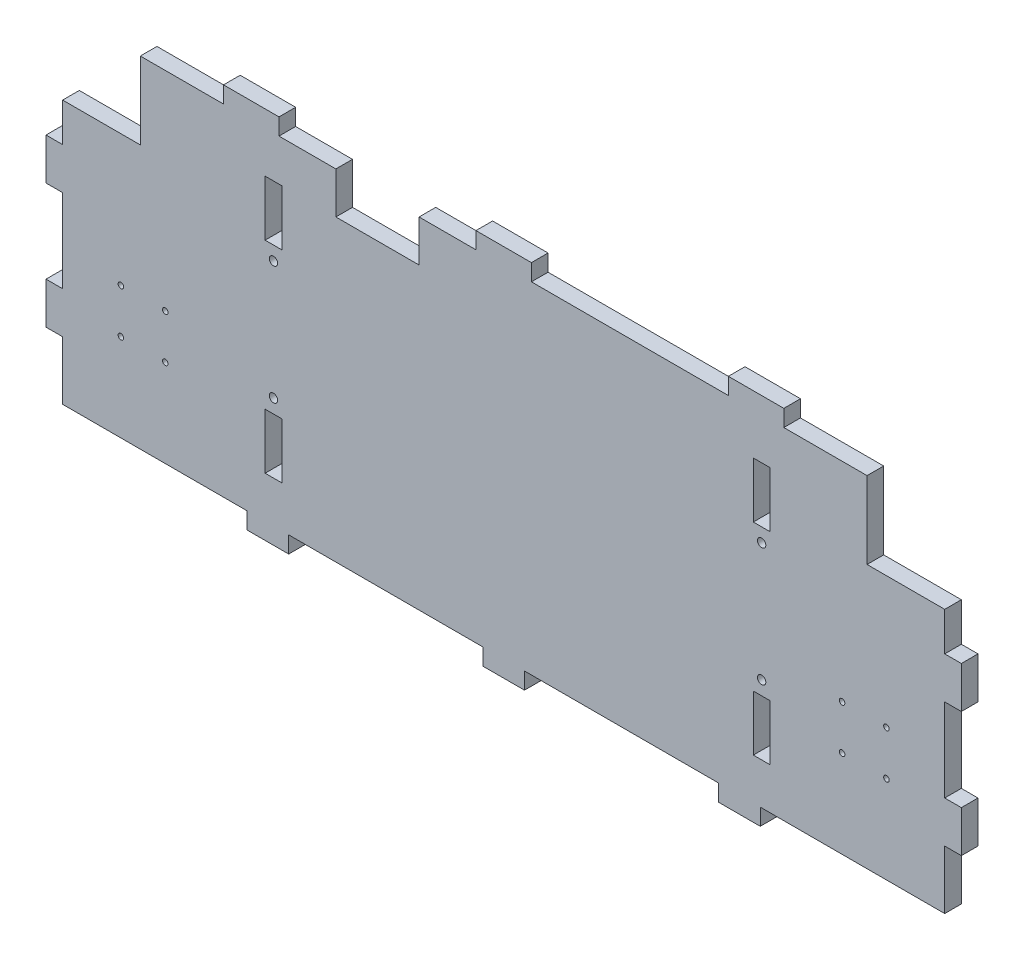
SolidWorks part; units mm, degrees
ref_plane "Plan de face" through (0, 0, 0) normal (0, 0, 1) x (1, 0, 0)
ref_plane "Plan de dessus" through (0, 0, 0) normal (0, 1, 0) x (1, 0, 0)
ref_plane "Plan de droite" through (0, 0, 0) normal (1, 0, 0) x (0, 0, -1)
sketch "Esquisse1" plane through (0, 0, 0) normal (0, 0, 1) x (1, 0, 0)
  line L0 (-159, 35) -> (-131, 35)
  line L1 (0, 102.0551) -> (0, -193.4247) construction
  line L2 (-159, 35) -> (-159, -60)
  line L3 (-159, -60) -> (159, -60)
  line L4 (159, 35) -> (159, -60)
  line L6 (131, 35) -> (131, 62.75)
  line L7 (131, 62.75) -> (-131, 62.75)
  line L8 (-131, 35) -> (-131, 62.75)
  line L9 (159, 35) -> (131, 35)
  line L10 (96, 47.75) -> (90, 47.75)
  line L11 (96, 47.75) -> (96, 27.75)
  line L12 (96, 27.75) -> (90, 27.75)
  line L13 (90, 47.75) -> (90, 27.75)
  line L14 (96, -25.01) -> (90, -25.01)
  line L15 (96, -25.01) -> (96, -45.01)
  line L16 (96, -45.01) -> (90, -45.01)
  line L17 (90, -25.01) -> (90, -45.01)
  line L18 (-80, 47.75) -> (-86, 47.75)
  line L19 (-80, 47.75) -> (-80, 27.75)
  line L20 (-80, 27.75) -> (-86, 27.75)
  line L21 (-86, 47.75) -> (-86, 27.75)
  line L22 (-80, -25.01) -> (-86, -25.01)
  line L23 (-80, -25.01) -> (-80, -45.01)
  line L24 (-80, -45.01) -> (-86, -45.01)
  line L25 (-86, -25.01) -> (-86, -45.01)
  dimension "D1" = 95
  dimension "D2" = 28
  dimension "D3" = 28
  dimension "D4" = 95
  dimension "D6" = 262
  dimension "D7" = 122.75
  dimension "D5" = 159
  dimension "D8" = 318
  dimension "D9" = 6
  dimension "D10" = 20
  dimension "D11" = 20
  dimension "D12" = 6
  dimension "D13" = 6
  dimension "D14" = 20
  dimension "D15" = 6
  dimension "D16" = 20
  dimension "D17" = 52.76
  dimension "D18" = 63
  dimension "D19" = 73
  dimension "D20" = 73
  dimension "D21" = 52.76
  dimension "D22" = 15
  dimension "D23" = 15
  dimension "D24" = 63
extrude "Boss.-Extru.1" add sketch "Esquisse1" along normal blind 6
sketch "Esquisse2" plane through (0, 0, 6) normal (0, 0, 1) x (1, 0, 0)
  line L0 (-159, -60) -> (159, -60) construction
  line L1 (-92.5, -60) -> (-77.5, -60)
  line L2 (-92.5, -60) -> (-92.5, -66)
  line L3 (-92.5, -66) -> (-77.5, -66)
  line L4 (-77.5, -60) -> (-77.5, -66)
  line L5 (-159, 35) -> (-159, -60) construction
  line L6 (-7.5, -60) -> (7.5, -60)
  line L7 (-7.5, -60) -> (-7.5, -66)
  line L8 (-7.5, -66) -> (7.5, -66)
  line L9 (7.5, -60) -> (7.5, -66)
  line L10 (77.5, -60) -> (92.5, -60)
  line L11 (77.5, -60) -> (77.5, -66)
  line L12 (77.5, -66) -> (92.5, -66)
  line L13 (92.5, -60) -> (92.5, -66)
  line L14 (176.2958, 0) -> (-249.7093, -3.2925) construction
  line L15 (0, 107.6082) -> (0, -117.4775) construction
  line L16 (-131, 35) -> (-159, 35) construction
  line L17 (-159, 21.09) -> (-165, 21.09)
  line L18 (-159, 21.09) -> (-159, 6.09)
  line L19 (-159, 6.09) -> (-165, 6.09)
  line L20 (-165, 21.09) -> (-165, 6.09)
  line L21 (-159, -23.91) -> (-165, -23.91)
  line L22 (-159, -23.91) -> (-159, -38.91)
  line L23 (-159, -38.91) -> (-165, -38.91)
  line L24 (-165, -23.91) -> (-165, -38.91)
  line L25 (165, -23.91) -> (165, -38.91)
  line L26 (159, -38.91) -> (165, -38.91)
  line L27 (159, -23.91) -> (159, -38.91)
  line L28 (159, -23.91) -> (165, -23.91)
  line L29 (165, 21.09) -> (165, 6.09)
  line L30 (159, 6.09) -> (165, 6.09)
  line L31 (159, 21.09) -> (159, 6.09)
  line L32 (159, 21.09) -> (165, 21.09)
  line L33 (131, 62.75) -> (-131, 62.75) construction
  line L34 (101, 62.75) -> (81, 62.75)
  line L35 (101, 62.75) -> (101, 68.75)
  line L36 (101, 68.75) -> (81, 68.75)
  line L37 (81, 62.75) -> (81, 68.75)
  line L38 (-131, 62.75) -> (-131, 35) construction
  line L39 (-81, 62.75) -> (-101, 62.75)
  line L40 (-81, 62.75) -> (-81, 68.75)
  line L41 (-81, 68.75) -> (-101, 68.75)
  line L42 (-101, 62.75) -> (-101, 68.75)
  line L43 (10, 62.75) -> (-10, 62.75)
  line L44 (10, 62.75) -> (10, 68.75)
  line L45 (10, 68.75) -> (-10, 68.75)
  line L46 (-10, 62.75) -> (-10, 68.75)
  line L47 (131, 35) -> (131, 62.75) construction
  dimension "D1" = 66.5
  dimension "D2" = 70
  dimension "D3" = 15
  dimension "D4" = 15
  dimension "D5" = 70
  dimension "D6" = 15
  dimension "D7" = 6
  dimension "D8" = 6
  dimension "D9" = 6
  dimension "D10" = 6
  dimension "D11" = 13.91
  dimension "D12" = 15
  dimension "D13" = 30
  dimension "D14" = 15
  dimension "D15" = 20
  dimension "D16" = 20
  dimension "D17" = 20
  dimension "D18" = 30
  dimension "D19" = 30
  dimension "D20" = 121
  dimension "D21" = 6
  dimension "D22" = 6
  dimension "D23" = 6
  dimension "D24" = 6
extrude "Boss.-Extru.2" add sketch "Esquisse2" against normal blind 6
sketch "Esquisse3" plane through (0, 0, 0) normal (0, 0, -1) x (-1, 0, 0)
  line L0 (159, -60) -> (92.5, -60) construction
  line L1 (159, 6.09) -> (159, -23.91) construction
  line L2 (0, 141.59) -> (0, -167.3887) construction
  line L3 (83, 57.185) -> (83, -52.5738) construction
  line L4 (-93, 52.3657) -> (-93, -53.0892) construction
  line L5 (-90, 27.75) -> (-96, 27.75) construction
  line L6 (-96, 27.75) -> (-96, 47.75) construction
  line L7 (-96, -25.01) -> (-90, -25.01) construction
  line L8 (80, -25.01) -> (86, -25.01) construction
  line L9 (80, -45.01) -> (80, -25.01) construction
  line L10 (86, 27.75) -> (80, 27.75) construction
  circle A0 centre (138, -28.38) radius 1
  circle A1 centre (138, -12.38) radius 1
  circle A2 centre (122, -12.38) radius 1
  circle A3 centre (122, -28.38) radius 1
  circle A4 centre (-122, -28.38) radius 1
  circle A5 centre (-122, -12.38) radius 1
  circle A6 centre (-138, -12.38) radius 1
  circle A7 centre (-138, -28.38) radius 1
  circle A9 centre (83, 22.75) radius 1.5
  circle A10 centre (83, -20.01) radius 1.5
  circle A13 centre (-93, 22.75) radius 1.5
  circle A14 centre (-93, -20.01) radius 1.5
  dimension "D1" = 31.62
  dimension "D2" = 21
  dimension "D7" = 2
  dimension "D8" = 2
  dimension "D9" = 2
  dimension "D10" = 2
  dimension "D11" = 3
  dimension "D12" = 3
  dimension "D13" = 3
  dimension "D14" = 3
  dimension "D17" = 5
  dimension "D18" = 5
  dimension "D20" = 5
  dimension "D3" = 16
  dimension "D4" = 16
  dimension "D5" = 16
  dimension "D6" = 16
  dimension "D15" = 5
  dimension "D16" = 3
  dimension "D19" = 3
extrude "Enlèv. mat.-Extru.1" cut sketch "Esquisse3" against normal blind 6
sketch "Esquisse4" plane through (0, 0, 0) normal (0, 0, -1) x (-1, 0, 0)
  line L0 (10, 62.75) -> (81, 62.75) construction
  line L1 (30.5, 62.75) -> (60.5, 62.75)
  line L2 (30.5, 62.75) -> (30.5, 47.75)
  line L3 (30.5, 47.75) -> (60.5, 47.75)
  line L4 (60.5, 62.75) -> (60.5, 47.75)
  line L5 (10, 68.75) -> (10, 62.75) construction
  dimension "D1" = 20.5
  dimension "D2" = 30
  dimension "D3" = 15
extrude "Enlèv. mat.-Extru.2" cut sketch "Esquisse4" against normal blind 6
equation "\"D5@Esquisse1\"=\"D8@Esquisse1\"/2"
